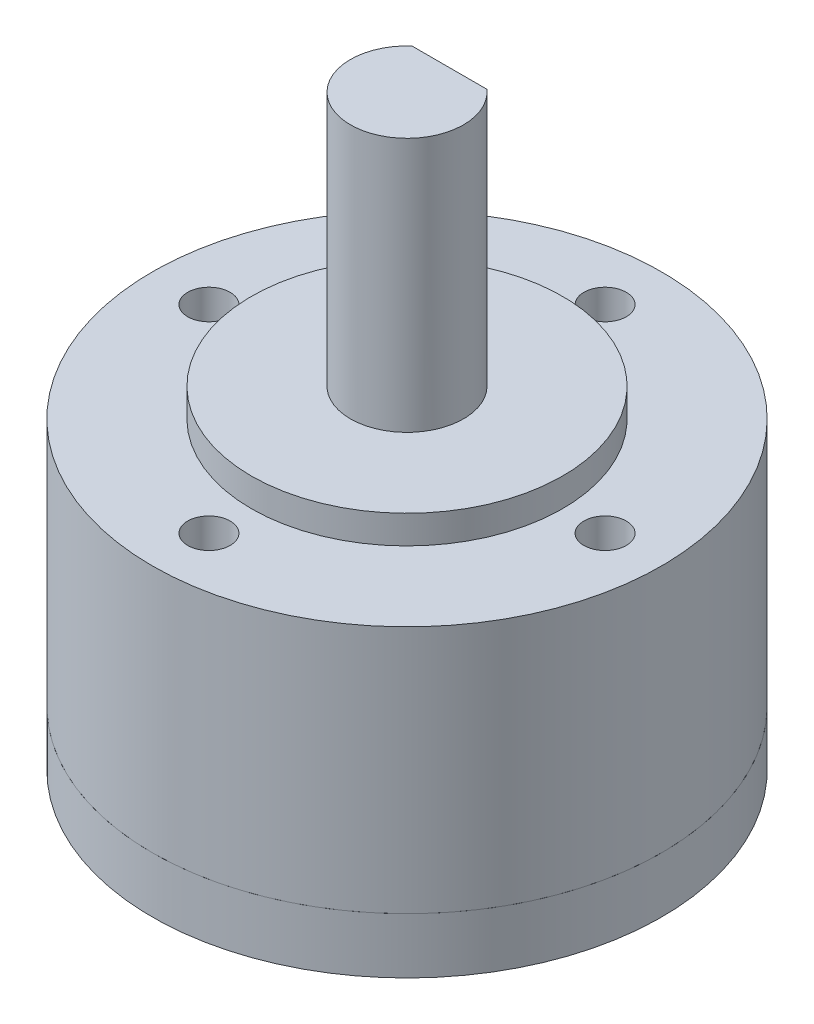
SolidWorks part; units mm, degrees
ref_plane "Front Plane" through (0, 0, 0) normal (0, 0, 1) x (1, 0, 0)
ref_plane "Top Plane" through (0, 0, 0) normal (0, 1, 0) x (1, 0, 0)
ref_plane "Right Plane" through (0, 0, 0) normal (1, 0, 0) x (0, 0, -1)
sketch "Sketch1" plane through (0, 0, 0) normal (0, 1, 0) x (1, 0, 0)
  circle A0 centre (0, 0) radius 18
  dimension "D1" = 36
extrude "Boss-Extrude1" add sketch "Sketch1" along normal mid plane 17.559
sketch "Sketch2" plane through (0, 8.7795, 0) normal (0, 1, 0) x (1, 0, 0)
  circle A0 centre (0, 0) radius 11
  dimension "D1" = 22
extrude "Boss-Extrude2" add sketch "Sketch2" along normal blind 2
sketch "Sketch3" plane through (0, 10.7795, 0) normal (0, 1, 0) x (1, 0, 0)
  circle A0 centre (0, 0) radius 4
  dimension "D1" = 8
extrude "Boss-Extrude4" add sketch "Sketch3" along normal blind 18
sketch "Sketch4" plane through (0, 28.7795, 0) normal (0, 1, 0) x (1, 0, 0)
  line L0 (-2.6458, 3) -> (2.6458, 3)
  line L1 (0, -4) -> (0, 3) construction
  arc A0 (0, -4) -> (2.6458, 3) centre (0, 0) ccw construction
  circle A1 centre (0, 0) radius 4
  arc A2 (2.6458, 3) -> (-2.6458, 3) centre (0, 0) ccw
  arc A3 (-2.6458, 3) -> (0, -4) centre (0, 0) ccw construction
  dimension "D2" = 7
  dimension "D1" = 0
extrude "Cut-Extrude1" cut sketch "Sketch4" against normal blind 15
sketch "Sketch5" plane through (0, 8.7795, 0) normal (0, 1, 0) x (1, 0, 0)
  circle A0 centre (0, 0) radius 14 construction
  circle A1 centre (0, 14) radius 1.5
  circle A2 centre (-14, 0) radius 1.5
  circle A3 centre (0, -14) radius 1.5
  circle A4 centre (14, 0) radius 1.5
  dimension "D1" = 28
  dimension "D2" = 3
extrude "Cut-Extrude2" cut sketch "Sketch5" against normal through all
sketch "Sketch6" plane through (0, -8.7795, 0) normal (0, -1, 0) x (1, 0, 0)
  circle A0 centre (0, 0) radius 11.178
  dimension "D1" = 22.356
extrude "Cut-Extrude3" cut sketch "Sketch6" against normal offset from surface (12.559 mm away) 5 up to face at (0, 8.7795, -12.5)
sketch "Sketch7" plane through (0, -8.7795, 0) normal (0, -1, 0) x (1, 0, 0)
  circle A1 centre (0, 0) radius 18
  circle A2 centre (0, 0) radius 18
  dimension "D1" = 0
extrude "Boss-Extrude5" add sketch "Sketch7" along normal blind 3.937 separate body
sketch "Sketch8" plane through (0, -8.7795, 0) normal (0, 1, 0) x (1, 0, 0)
  circle A0 centre (0, 0) radius 10.9855
  dimension "D1" = 21.971
extrude "Boss-Extrude6" add sketch "Sketch8" along normal blind 2.413
sketch "Sketch9" plane through (0, -8.7795, 0) normal (0, 1, 0) x (1, 0, 0)
  circle A0 centre (0, 14) radius 1.265
  circle A1 centre (14, 0) radius 1.265
  circle A2 centre (0, -14) radius 1.265
  circle A3 centre (-14, 0) radius 1.265
  dimension "D1" = 2.53
extrude "Cut-Extrude4" cut sketch "Sketch9" against normal through all
sketch "Sketch10" plane through (0, -6.3665, 0) normal (0, 1, 0) x (1, 0, 0)
  circle A0 centre (0, 0) radius 4
  dimension "D1" = 8
extrude "Cut-Extrude5" cut sketch "Sketch10" against normal through all
sketch "Sketch11" plane through (0, -6.3665, 0) normal (0, 1, 0) x (1, 0, 0)
  circle A0 centre (0, 0) radius 4.75
  dimension "D1" = 9.5
extrude "Cut-Extrude6" cut sketch "Sketch11" against normal blind 0.6
